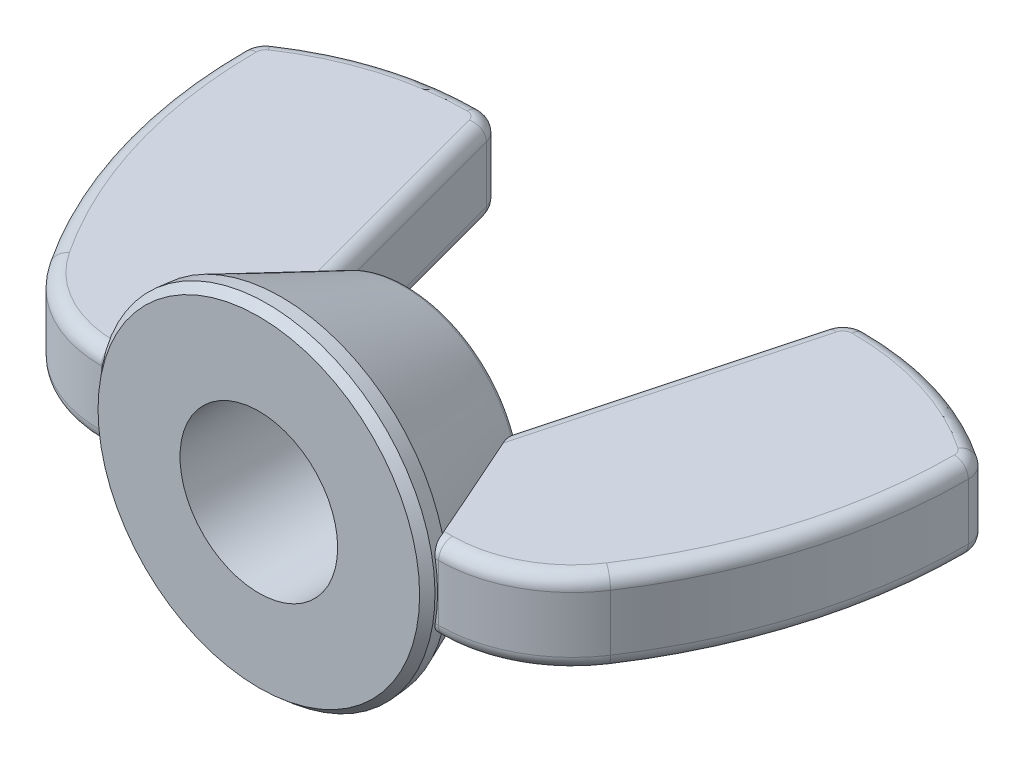
SolidWorks part; units mm, degrees
ref_plane "Front Plane" through (0, 0, 0) normal (0, 0, 1) x (1, 0, 0)
ref_plane "Top Plane" through (0, 0, 0) normal (0, 1, 0) x (1, 0, 0)
ref_plane "Right Plane" through (0, 0, 0) normal (1, 0, 0) x (0, 0, -1)
sketch "Sketch1" plane through (0, 0, 0) normal (0, 0, 1) x (1, 0, 0)
  circle A0 centre (0, 0) radius 2.413
  circle A1 centre (0, 0) radius 5.1594
  dimension "D1" = 10.3187
sketch "Sketch2" plane through (0, 0, 0) normal (0, 1, 0) x (1, 0, 0)
  line L0 (0, 0) -> (0, 12.7) construction
  line L1 (-2.413, 0) -> (2.413, 0) construction
  line L2 (-11.1125, 12.7) -> (11.1125, 12.7) construction
  line L3 (11.1125, 12.7) -> (11.1125, 0) construction
  line L4 (-11.1125, 12.7) -> (-11.1125, 0) construction
  line L5 (-11.1125, 0) -> (11.1125, 0) construction
  line L6 (-3.5186, 4.572) -> (3.5186, 4.572) construction
  line L7 (0, 0) -> (0, 4.572) construction
  line L8 (-4.3144, 0.6858) -> (5.1594, 0.6858) construction
  line L9 (5.1594, 0) -> (5.1594, 4.572) construction
  line L10 (3.1667, 4.572) -> (5.3943, 12.8856)
  line L12 (3.5186, 4.572) -> (3.5186, 0.3429) construction
  line L13 (-5.1594, 0) -> (5.1594, 0) construction
  line L14 (5.1594, 0.6858) -> (3.5186, 4.572) construction
  line L15 (5.3943, 12.8856) -> (11.3449, 11.0664)
  line L16 (11.3449, 11.0664) -> (7.152, 0.3429)
  line L17 (5.1594, 0.3429) -> (7.152, 0.3429)
  line L19 (3.1667, 0.3429) -> (5.1594, 0.3429)
  line L20 (-3.1667, 4.572) -> (3.1667, 4.572) construction
  line L21 (3.1667, 4.572) -> (3.1667, 0.3429)
  circle A3 centre (10.3959, 10.6072) radius 0.7166 construction
  circle A4 centre (5.8945, 11.9834) radius 0.7166 construction
  dimension "D6" = 1.4332
  dimension "D2" = 4.572
  dimension "D4" = 7.0371
  dimension "D1" = 0.6858
  dimension "D3" = 22.89
  dimension "D5" = 0.3429
  dimension "D8" = 17
  dimension "D9" = 6.3334
  dimension "D7" = 15
sketch "Sketch13" plane through (0, 0, 0) normal (0, 1, 0) x (1, 0, 0)
  line L1 (3.1667, 4.572) -> (3.1667, 0.3429) construction
  line L2 (3.1667, 4.572) -> (5.3943, 12.8856) construction
  line L3 (-11.1125, 12.7) -> (11.1125, 12.7) construction
  line L4 (11.1125, 12.7) -> (11.1125, 0) construction
  line L5 (5.1594, 0.3429) -> (7.152, 0.3429) construction
  line L6 (3.1667, 0.3429) -> (5.1594, 0.3429) construction
  line L7 (0, 0) -> (0, 4.572) construction
  line L8 (-2.413, 0) -> (2.413, 0) construction
  line L9 (0, 0) -> (0, 12.7) construction
  line L10 (-3.5186, 4.572) -> (3.5186, 4.572) construction
  line L11 (3.1667, 0.3429) -> (5.1594, 0.3429)
  line L12 (3.1667, 4.572) -> (3.1667, 0.3429)
  line L13 (3.1667, 4.572) -> (5.2023, 12.1689)
  circle A0 centre (10.3959, 10.6072) radius 0.7166 construction
  circle A1 centre (5.8945, 11.9834) radius 0.7166 construction
  arc A5 (11.1125, 10.6072) -> (10.7966, 11.2013) centre (10.3959, 10.6072) ccw
  arc A6 (5.8945, 12.7) -> (5.2023, 12.1689) centre (5.8945, 11.9834) ccw
  arc A7 (8.5807, 2.183) -> (11.1125, 10.6072) centre (-4.1686, 10.6072) ccw
  arc A8 (10.7966, 11.2013) -> (5.8945, 12.7) centre (5.8945, 3.9335) ccw
  arc A10 (5.1594, 0.3429) -> (8.5807, 2.183) centre (5.1594, 4.4437) ccw
extrude "Extrude2" add sketch "Sketch13" along normal mid plane 2.5797
sketch "Sketch3" plane through (0, 0, 0) normal (0, 0, 1) x (1, 0, 0)
  circle A0 centre (0, 0) radius 5.1594 construction
  circle A1 centre (0, 0) radius 5.1594
extrude "Extrude1" add sketch "Sketch3" against normal up to vertex (0.6858 mm away) draft 5 separate body up to point (5.1594, 0, -0.6858)
sketch "Sketch15" plane through (0, 0, -0.6858) normal (0, 0, -1) x (-1, 0, 0)
  circle A1 centre (0, 0) radius 5.0994
  circle A2 centre (0, 0) radius 5.0994
  dimension "D1" = 0
extrude "Extrude3" add sketch "Sketch15" along normal up to vertex (3.8862 mm away) draft 22.89 up to point (0, 0, -4.572)
fillet "Fillet3" radius 0.254 1 edges at (-3.4586, 0, -4.572)
sketch "Sketch12" plane through (0, 0, -4.572) normal (0, 0, -1) x (-1, 0, 0)
  circle A1 centre (0, 0) radius 5.0994
  circle A2 centre (0, 0) radius 5.0994 construction
  dimension "D1" = 10.1988
sketch "Sketch4" plane through (0, 0, 0) normal (0, 0, 1) x (1, 0, 0)
  circle A0 centre (0, 0) radius 2.413 construction
  circle A1 centre (0, 0) radius 2.413
extrude "Cut-Extrude1" cut sketch "Sketch4" against normal through all
sketch "Sketch5" plane through (0, 0, 0) normal (0, 0, 1) x (1, 0, 0)
  circle A0 centre (0, 0) radius 2.413 construction
  circle A1 centre (0, 0) radius 2.413
curve "Helix/Spiral1" pitch 0.7937 height 7.747 turns 9.76 parameters "pitch"=0.7937
sketch "Sketch6" plane through (0, 0, 0) normal (0, 1, 0) x (1, 0, 0)
  line L0 (-2.413, -0.6945) -> (-1.8974, -0.3969)
  line L1 (-1.8974, -0.3969) -> (-1.8974, -0.2977)
  line L2 (-1.8974, -0.2977) -> (-2.413, 0)
  line L3 (-2.413, -0.6945) -> (-2.413, 0)
  line L4 (-2.413, -0.3473) -> (-1.8974, -0.3473) construction
  line L5 (-2.1552, -0.5457) -> (-2.1552, -0.1488) construction
  line L6 (-2.413, 0) -> (2.413, 0) construction
  dimension "D1" = 60
  dimension "D2" = 0.0992
  dimension "D3" = 0.3969
sweep "Sweep1" [suppressed] add profiles "Sketch6" path "Helix/Spiral1"
sketch "Sketch7" plane through (0, 0, 0) normal (0, 0, 1) x (1, 0, 0)
  circle A1 centre (0, 0) radius 5.1594
  circle A2 centre (0, 0) radius 5.1594
  dimension "D1" = 0
extrude "Cut-Extrude2" [suppressed] cut sketch "Sketch7" along normal through all
ref_plane "Plane1" through (0, 0, -4.572) normal (0, 0, 1) x (1, 0, 0)
sketch "Sketch8" plane through (0, 0, -4.572) normal (0, 0, 1) x (1, 0, 0)
  circle A0 centre (0, 0) radius 5.0994 construction
  circle A2 centre (0, 0) radius 5.0994
extrude "Cut-Extrude3" [suppressed] cut sketch "Sketch8" against normal through all
sketch "Sketch9" plane through (0, 0, 0) normal (0, 0, 1) x (1, 0, 0)
  circle A1 centre (0, 0) radius 2.413
  circle A2 centre (0, 0) radius 2.413
  dimension "D1" = 0
extrude "Cut-Extrude4" [suppressed] cut sketch "Sketch9" against normal through all draft 45
sketch "Sketch11" plane through (0, 0, -4.572) normal (0, 0, 1) x (1, 0, 0)
  circle A0 centre (0, 0) radius 2.413 construction
  circle A1 centre (0, 0) radius 2.3622
  circle A2 centre (0, 0) radius 2.413 construction
  dimension "D1" = 0.0508
extrude "Cut-Extrude5" [suppressed] cut sketch "Sketch11" along normal through all draft 45
chamfer "Chamfer1" distance 0.2572 angle 45 1 edges at (5.1594, 0, 0) first distance on face at (-5.0994, 0, -0.6858)
fillet "Fillet4" radius 0.4299 14 edges at (4.163, 1.2898, -0.3429) (7.1018, 1.2898, -0.8321) (5.4582, 1.2898, -12.5519) (8.4575, 1.2898, -12.3169) (11.0286, 1.2898, -10.9436) (4.163, -1.2898, -0.3429) (7.1018, -1.2898, -0.8321) (5.4582, -1.2898, -12.5519) (8.4575, -1.2898, -12.3169) (11.0286, -1.2898, -10.9436) (10.4659, 1.2898, -6.209) (10.4659, -1.2898, -6.209) (4.1845, 1.2898, -8.3704) (4.1845, -1.2898, -8.3704)
mirror "Mirror6" about plane through (0, 0, 0) normal (1, 0, 0) of bodies 108 113
combine bodies "Combine2" operation type add bodies to combine 116 108 102
equation "\"D1@Sketch1\" = \"thread dia@Sketch1\"*1.725"
equation "\"D2@Sketch2\" = \"B@Sketch2\"*.36"
equation "\"D3@Helix/Spiral1\" = \"D2@Sketch2\"+.125"
equation "\"D2@Sketch6\" = \"pitch@Helix/Spiral1\"*.125"
equation "\"D3@Sketch6\" = \"pitch@Helix/Spiral1\"*.5"
equation "\"D4@Sketch2\" = \"D1@Sketch12\"*.69"
equation "\"D1@Extrude2\" = \"D1@Sketch1\"*.25"
equation "\"D1@Sketch2\" = \"D2@Sketch2\"*.150"
equation "\"D5@Sketch2\" = \"D1@Sketch2\"/2"
equation "\"D3@Extrude3\" = \"D3@Sketch2\""
equation "\"D1@Chamfer1\" = \"D5@Sketch2\"*.75"
equation "\"D9@Sketch2\" = \"D4@Sketch2\"*.9"
equation "\"D6@Sketch2\" = \"D1@Extrude2\"/1.8"
equation "\"D1@Fillet4\" = \"D1@Extrude2\"/6"
